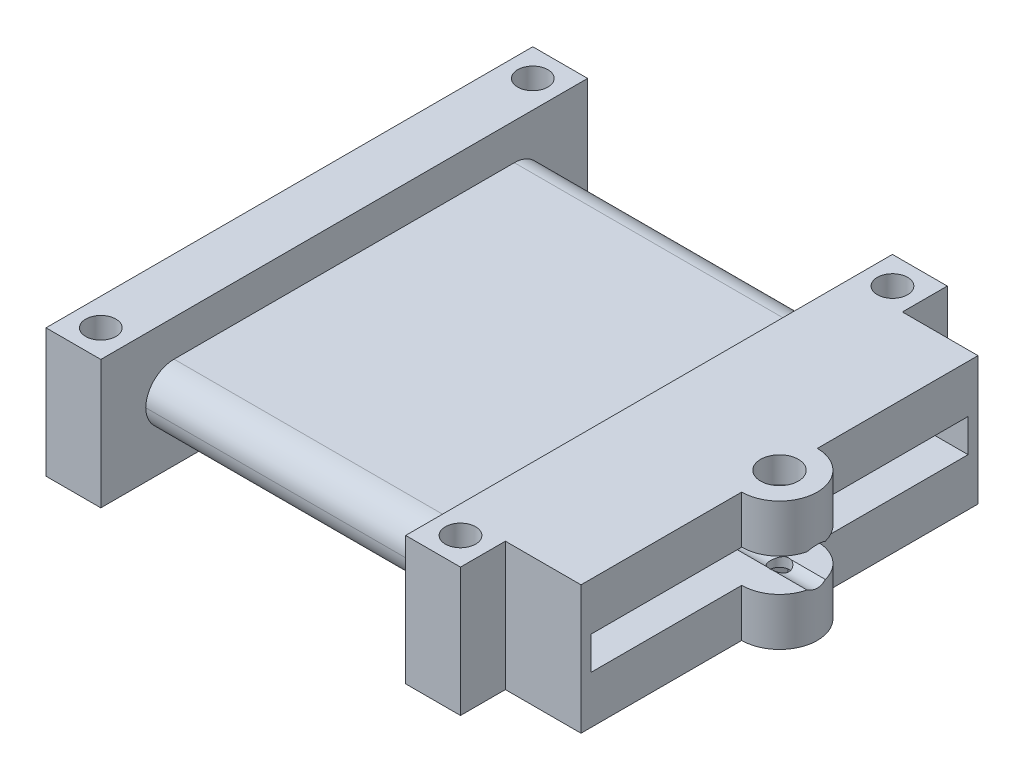
SolidWorks part; units mm, degrees
ref_plane "Front Plane" through (0, 0, 0) normal (0, 0, 1) x (1, 0, 0)
ref_plane "Top Plane" through (0, 0, 0) normal (0, 1, 0) x (1, 0, 0)
ref_plane "Right Plane" through (0, 0, 0) normal (1, 0, 0) x (0, 0, -1)
sketch "Sketch1" plane through (0, 0, 0) normal (1, 0, 0) x (0, 0, -1)
  line L0 (21, 5.9) -> (21, 0) construction
  line L1 (0, 0) -> (42, 0)
  line L2 (0, 0) -> (0, 5.9)
  line L3 (0, 5.9) -> (42, 5.9)
  line L4 (42, 0) -> (42, 5.9)
  line L6 (1.05, 1.2) -> (40.95, 1.2)
  line L7 (1.05, 1.2) -> (1.05, 4.7)
  line L8 (1.05, 4.7) -> (40.95, 4.7)
  line L9 (40.95, 1.2) -> (40.95, 4.7)
  line L10 (1.05, 1.2) -> (40.95, 4.7) construction
  line L11 (1.05, 4.7) -> (40.95, 1.2) construction
  point P7 (21, 2.95)
  dimension "D1" = 42
  dimension "D2" = 5.9
  dimension "D3" = 3.5
  dimension "D4" = 39.9
extrude "Boss-Extrude1" add sketch "Sketch1" along normal blind 32.25
fillet "Fillet2" radius 3 4 edges at (16.125, 0, -42) (16.125, 0, 0) (16.125, 5.9, 0) (16.125, 5.9, -42)
sketch "Sketch2" plane through (32.25, 0, 0) normal (1, 0, 0) x (0, 0, -1)
  line L0 (21, 5.9) -> (21, 0) construction
  line L1 (39, 5.9) -> (3, 5.9) construction
  line L2 (3, 0) -> (39, 0) construction
  line L4 (-4.75, -3.85) -> (46.75, -3.85)
  line L5 (-4.75, -3.85) -> (-4.75, 9.75)
  line L6 (-4.75, 9.75) -> (46.75, 9.75)
  line L7 (46.75, -3.85) -> (46.75, 9.75)
  line L8 (-4.75, -3.85) -> (46.75, 9.75) construction
  line L9 (-4.75, 9.75) -> (46.75, -3.85) construction
  line L14 (40.95, 1.2) -> (1.05, 1.2)
  line L15 (40.95, 1.2) -> (40.95, 4.7)
  line L16 (40.95, 4.7) -> (1.05, 4.7)
  line L17 (1.05, 1.2) -> (1.05, 4.7)
  line L18 (40.95, 1.2) -> (1.05, 4.7) construction
  line L19 (40.95, 4.7) -> (1.05, 1.2) construction
  point P6 (21, 2.95)
  point P11 (21, 2.95)
  point P12 (21, 2.95)
  dimension "D1" = 13.6
  dimension "D2" = 51.5
extrude "Boss-Extrude2" add sketch "Sketch2" along normal blind 5.8
sketch "Sketch3" plane through (0, 0, 0) normal (-1, 0, 0) x (0, 0, 1)
  line L0 (-21, 5.9) -> (-21, 0) construction
  line L1 (-39, 5.9) -> (-3, 5.9) construction
  line L2 (-3, 0) -> (-39, 0) construction
  line L4 (4.75, -3.85) -> (-46.75, -3.85)
  line L5 (4.75, -3.85) -> (4.75, 9.75)
  line L6 (4.75, 9.75) -> (-46.75, 9.75)
  line L7 (-46.75, -3.85) -> (-46.75, 9.75)
  line L8 (4.75, -3.85) -> (-46.75, 9.75) construction
  line L9 (4.75, 9.75) -> (-46.75, -3.85) construction
  line L10 (-1.05, 1.2) -> (-40.95, 1.2)
  line L11 (-1.05, 1.2) -> (-1.05, 4.7)
  line L12 (-1.05, 4.7) -> (-40.95, 4.7)
  line L13 (-40.95, 1.2) -> (-40.95, 4.7)
  line L14 (-1.05, 1.2) -> (-40.95, 4.7) construction
  line L15 (-1.05, 4.7) -> (-40.95, 1.2) construction
  point P6 (-21, 2.95)
  point P12 (-21, 2.95)
extrude "Boss-Extrude3" add sketch "Sketch3" along normal blind 5.8
sketch "Sketch4" plane through (0, 9.75, 0) normal (0, 1, 0) x (1, 0, 0)
  line L0 (-2.9, 46.75) -> (-2.9, 43.85) construction
  line L1 (-5.8, 46.75) -> (0, 46.75) construction
  line L2 (35.15, 46.75) -> (35.15, 43.85) construction
  line L3 (38.05, 46.75) -> (32.25, 46.75) construction
  line L4 (-2.9, -4.75) -> (-2.9, -1.85) construction
  line L5 (-5.8, -4.75) -> (0, -4.75) construction
  line L6 (35.15, -4.75) -> (35.15, -1.85) construction
  line L7 (38.05, -4.75) -> (32.25, -4.75) construction
  circle A0 centre (-2.9, 43.85) radius 1.6
  circle A1 centre (35.15, 43.85) radius 1.6
  circle A2 centre (-2.9, -1.85) radius 1.6
  circle A3 centre (35.15, -1.85) radius 1.6
  dimension "D2" = 3.2
  dimension "D4" = 3.2
  dimension "D6" = 3.2
  dimension "D8" = 3.2
  dimension "D1" = 2.9
  dimension "D3" = 2.9
  dimension "D5" = 2.9
  dimension "D7" = 2.9
extrude "Cut-Extrude1" cut sketch "Sketch4" against normal through all
sketch "Sketch6" plane through (38.05, 0, 0) normal (1, 0, 0) x (0, 0, -1)
  line L0 (46.75, -3.85) -> (46.75, 9.75) construction
  line L1 (-4.75, -3.85) -> (46.75, -3.85)
  line L2 (-4.75, -3.85) -> (-4.75, 3.35)
  line L3 (-4.75, 3.35) -> (46.75, 3.35)
  line L4 (46.75, -3.85) -> (46.75, 3.35)
  dimension "D1" = 7.2
extrude "Cut-Extrude2" [suppressed] cut sketch "Sketch6" against normal blind 5.8
sketch "Sketch7" plane through (-5.8, 0, 0) normal (-1, 0, 0) x (0, 0, 1)
  line L0 (4.75, -3.85) -> (4.75, 9.75) construction
  line L1 (-46.75, -3.85) -> (4.75, -3.85)
  line L2 (-46.75, -3.85) -> (-46.75, 3.35)
  line L3 (-46.75, 3.35) -> (4.75, 3.35)
  line L4 (4.75, -3.85) -> (4.75, 3.35)
  dimension "D1" = 7.2
extrude "Cut-Extrude3" [suppressed] cut sketch "Sketch7" against normal blind 5.8
sketch "Sketch8" plane through (0, 9.75, 0) normal (0, 1, 0) x (1, 0, 0)
  line L1 (0, 41.9996) -> (32.25, 41.9996) construction
  line L2 (38.05, 46.75) -> (38.05, -4.75) construction
  line L3 (46.05, 25) -> (46.05, 41.9996)
  line L4 (46.05, 41.9996) -> (38.05, 41.9996)
  line L5 (46.05, 17) -> (46.05, 0.0004)
  line L6 (46.05, 0.0004) -> (38.05, 0.0004)
  line L12 (-42.1211, 21) -> (79.5205, 21) construction
  line L13 (-5.8, -4.75) -> (-5.8, 46.75) construction
  circle A0 centre (46.05, 21) radius 4
  point P17 (-5.8, 21)
  line M5 (38.05, -4.75) -> (38.05, 46.75)
  dimension "D1" = 8
  dimension "D2" = 8
extrude "Boss-Extrude4" add sketch "Sketch8" against normal blind 13.6 contours A0 L3 L4 M5 | A0 L6 L5 M5 | A0 | A0 L12 region at (41.8639, 9.75, -32.2114) region at (46.05, 9.75, -22.6977) region at (46.05, 9.75, -19.3023) region at (41.8639, 9.75, -9.7886)
hole_wizard "CSK for M2 Flat Head Machine Screw1" positions "Sketch12" profile "Sketch13" countersink size "M2" standard "ANSI Metric" end condition through all
sketch "Sketch12" plane through (0, 9.75, 0) normal (0, 1, 0) x (1, 0, 0)
  point P0 (46.05, 21)
sketch "Sketch13" plane through (46.05, 9.75, -21) normal (1, 0, 0) x (0, 0, 1)
  line L0 (0, 0) -> (0, 13.6)
  line L1 (0, 13.6) -> (1, 13.6)
  line L2 (1, 13.6) -> (1, 3.75)
  line L3 (1, 3.75) -> (2, 2.75)
  line L4 (2, 2.75) -> (2, 0)
  line L6 (2, 0) -> (0, 0)
  line L7 (-1, 3.75) -> (-2, 2.75) construction
  line L11 (0, -6.35) -> (0, 107.95) construction
  dimension "Thru Hole Dia." = 2
  dimension "Thru Hole Depth" = 13.6
  dimension "C'Sink Dia." = 4
  dimension "C'Sink Angle" = 90
  dimension "Head Clearance" = 2.75
sketch "Sketch14" plane through (0, -3.85, 0) normal (0, -1, 0) x (1, 0, 0)
  line L1 (43.6251, -21) -> (44.8376, -23.1)
  line L2 (44.8376, -23.1) -> (47.2624, -23.1)
  line L3 (47.2624, -23.1) -> (48.4749, -21)
  line L4 (48.4749, -21) -> (47.2624, -18.9)
  line L5 (47.2624, -18.9) -> (44.8376, -18.9)
  line L6 (44.8376, -18.9) -> (43.6251, -21)
  circle A0 centre (46.05, -21) radius 2.1 construction
  dimension "D1" = 4.2
extrude "Cut-Extrude4" cut sketch "Sketch14" against normal blind 4
sketch "Sketch15" plane through (-5.8, 0, 0) normal (-1, 0, 0) x (0, 0, 1)
  line L1 (-40.95, 1.2) -> (-1.05, 1.2)
  line L2 (-40.95, 1.2) -> (-40.95, 4.7)
  line L3 (-40.95, 4.7) -> (-1.05, 4.7)
  line L4 (-1.05, 1.2) -> (-1.05, 4.7)
  line L5 (-46.75, -3.85) -> (-40.95, -3.85)
  line L6 (-46.75, -3.85) -> (-46.75, -1.85)
  line L7 (-46.75, -1.85) -> (-40.95, -1.85)
  line L8 (-40.95, -3.85) -> (-40.95, -1.85)
  line L9 (4.75, -3.85) -> (-1.05, -3.85)
  line L10 (4.75, -3.85) -> (4.75, -1.85)
  line L11 (4.75, -1.85) -> (-1.05, -1.85)
  line L12 (-1.05, -3.85) -> (-1.05, -1.85)
  dimension "D1" = 5.8
  dimension "D2" = 2
  dimension "D3" = 5.8
  dimension "D4" = 2
extrude "Cut-Extrude5" cut sketch "Sketch15" against normal through all contours L2 L1 L4 L3
sketch "Sketch17" plane through (-5.8, 0, 0) normal (-1, 0, 0) x (0, 0, 1)
  line L0 (-21, 4.7) -> (-21, 1.2) construction
  line L1 (-1.05, 4.7) -> (-40.95, 4.7) construction
  line L2 (-40.95, 1.2) -> (-1.05, 1.2) construction
  circle A0 centre (-21, 2.95) radius 2
  dimension "D1" = 4
extrude "Cut-Extrude6" cut sketch "Sketch17" against normal through all
